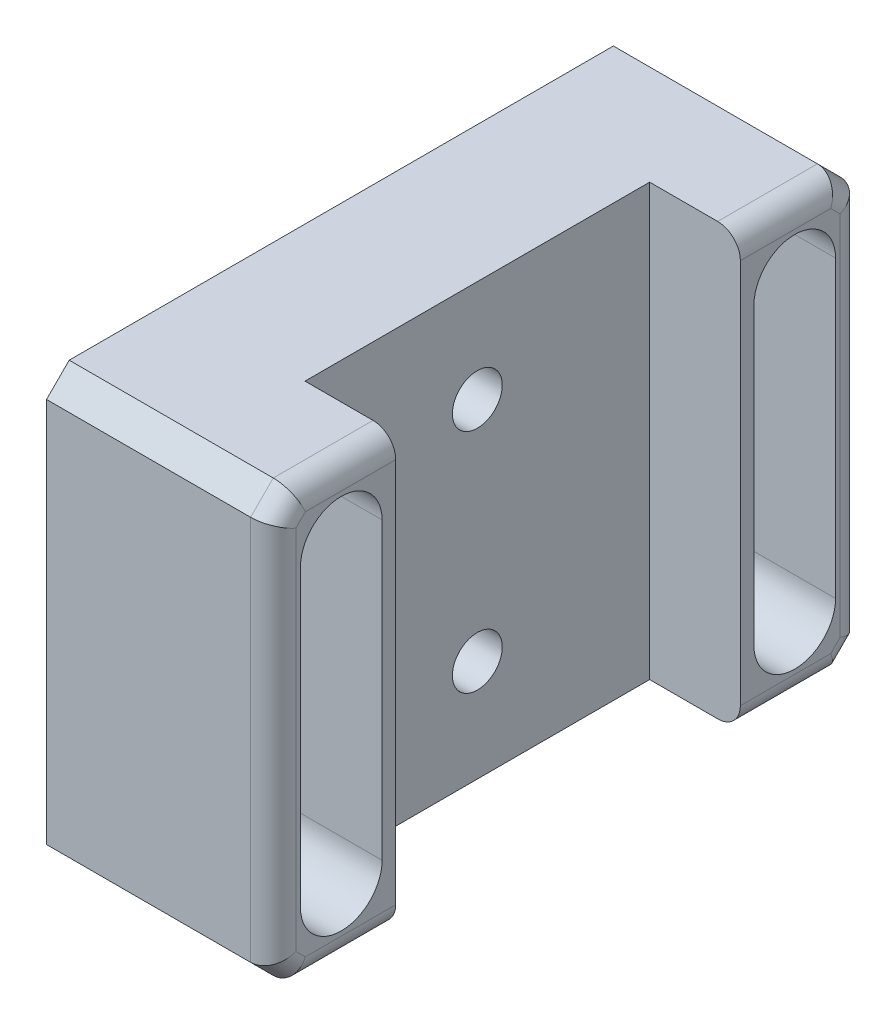
SolidWorks part; units mm, degrees
ref_plane "Спереди" through (0, 0, 0) normal (0, 0, 1) x (1, 0, 0)
ref_plane "Сверху" through (0, 0, 0) normal (0, 1, 0) x (1, 0, 0)
ref_plane "Справа" through (0, 0, 0) normal (1, 0, 0) x (0, 0, -1)
sketch "Эскиз1" plane through (0, 0, 0) normal (1, 0, 0) x (0, 0, -1)
  line L0 (-10, 6.5) -> (-10, -6.5) construction
  line L1 (-13, 9.5) -> (13, 9.5)
  line L2 (-13, 9.5) -> (-13, -9.5)
  line L3 (-13, -9.5) -> (13, -9.5)
  line L4 (13, 9.5) -> (13, -9.5)
  line L5 (-13, 9.5) -> (13, -9.5) construction
  line L6 (-13, -9.5) -> (13, 9.5) construction
  line L7 (-8.9, 6.5) -> (-8.9, -6.5)
  line L8 (-11.1, 6.5) -> (-11.1, -6.5)
  line L9 (0, 9.5) -> (0, -9.5) construction
  line L10 (10, 6.5) -> (10, -6.5) construction
  line L11 (8.9, 6.5) -> (8.9, -6.5)
  line L12 (11.1, 6.5) -> (11.1, -6.5)
  arc A0 (-8.9, 6.5) -> (-11.1, 6.5) centre (-10, 6.5) ccw
  arc A1 (-11.1, -6.5) -> (-8.9, -6.5) centre (-10, -6.5) ccw
  arc A2 (8.9, 6.5) -> (11.1, 6.5) centre (10, 6.5) cw
  arc A3 (11.1, -6.5) -> (8.9, -6.5) centre (10, -6.5) cw
  point P0 (0, 0)
  point P8 (-10, 0)
  point P17 (10, 0)
  dimension "D1" = 26
  dimension "D2" = 2.2
  dimension "D3" = 20
  dimension "D5" = 3
  dimension "D4" = 19
extrude "Бобышка-Вытянуть1" add sketch "Эскиз1" along normal blind 10
sketch "Эскиз2" plane through (10, 0, 0) normal (1, 0, 0) x (0, 0, -1)
  line L0 (-13, -9.5) -> (13, -9.5) construction
  line L1 (7.6, 9.5) -> (-7.6, 9.5)
  line L2 (7.6, 9.5) -> (7.6, -9.5)
  line L3 (7.6, -9.5) -> (-7.6, -9.5)
  line L4 (-7.6, 9.5) -> (-7.6, -9.5)
  line L5 (7.6, 9.5) -> (-7.6, -9.5) construction
  line L6 (7.6, -9.5) -> (-7.6, 9.5) construction
  point P0 (0, 0)
  dimension "D1" = 15.2
extrude "Вырез-Вытянуть1" cut sketch "Эскиз2" against normal blind 4
sketch "Эскиз3" plane through (10, 0, 0) normal (1, 0, 0) x (0, 0, -1)
  line L0 (-10, -6.5) -> (-10, 6.5) construction
  line L1 (-11.8, -6.5) -> (-11.8, 6.5)
  line L2 (-8.2, -6.5) -> (-8.2, 6.5)
  line L3 (0, 9.5) -> (0, -9.5) construction
  line L4 (7.6, 9.5) -> (-7.6, 9.5) construction
  line L5 (-7.6, -9.5) -> (7.6, -9.5) construction
  line L6 (10, -6.5) -> (10, 6.5) construction
  line L7 (11.8, -6.5) -> (11.8, 6.5)
  line L8 (8.2, -6.5) -> (8.2, 6.5)
  arc A0 (-11.8, -6.5) -> (-8.2, -6.5) centre (-10, -6.5) ccw
  arc A1 (-8.2, 6.5) -> (-11.8, 6.5) centre (-10, 6.5) ccw
  arc A2 (-11.1, -6.5) -> (-8.9, -6.5) centre (-10, -6.5) ccw construction
  arc A3 (-8.9, 6.5) -> (-11.1, 6.5) centre (-10, 6.5) ccw construction
  arc A4 (11.8, -6.5) -> (8.2, -6.5) centre (10, -6.5) cw
  arc A5 (8.2, 6.5) -> (11.8, 6.5) centre (10, 6.5) cw
  point P2 (-10, 0)
  point P23 (10, 0)
  dimension "D1" = 3.6
extrude "Вырез-Вытянуть2" cut sketch "Эскиз3" against normal blind 4
chamfer "Фаска1" distance 1 angle 45 4 edges at (5, 9.5, -13) (5, -9.5, -13) (5, -9.5, 13) (5, 9.5, 13)
fillet "Скругление1" radius 1 10 edges at (10, 9, 12.5) (10, -9, 12.5) (10, -9, -12.5) (10, -9.5, -9.8) (10, 0, -13) (10, 9, -12.5) (10, 9.5, -9.8) (10, -9.5, 9.8) (10, 9.5, 9.8) (10, 0, 13)
sketch "Эскиз4" plane through (6, 0, 0) normal (1, 0, 0) x (0, 0, -1)
  line L0 (0, 9.5) -> (0, -9.5) construction
  line L1 (7.6, 9.5) -> (-7.6, 9.5) construction
  line L2 (-7.6, -9.5) -> (7.6, -9.5) construction
  line L3 (-7.6, 0) -> (7.6, 0) construction
  line L4 (-7.6, 9.5) -> (-7.6, -9.5) construction
  line L5 (7.6, -9.5) -> (7.6, 9.5) construction
  circle A0 centre (0, 5) radius 1.1
  circle A1 centre (0, -5) radius 1.1
  dimension "D1" = 2.2
  dimension "D2" = 10
extrude "Вырез-Вытянуть3" cut sketch "Эскиз4" against normal through all
sketch "Эскиз5" plane through (0, 0, 0) normal (-1, 0, 0) x (0, 0, 1)
  line L1 (1.1258, 3.05) -> (2.2517, 5)
  line L2 (2.2517, 5) -> (1.1258, 6.95)
  line L3 (1.1258, 6.95) -> (-1.1258, 6.95)
  line L4 (-1.1258, 6.95) -> (-2.2517, 5)
  line L5 (-2.2517, 5) -> (-1.1258, 3.05)
  line L6 (-1.1258, 3.05) -> (1.1258, 3.05)
  line L7 (1.1258, -6.95) -> (2.2517, -5)
  line L8 (2.2517, -5) -> (1.1258, -3.05)
  line L9 (1.1258, -3.05) -> (-1.1258, -3.05)
  line L10 (-1.1258, -3.05) -> (-2.2517, -5)
  line L11 (-2.2517, -5) -> (-1.1258, -6.95)
  line L12 (-1.1258, -6.95) -> (1.1258, -6.95)
  circle A0 centre (0, 5) radius 1.95 construction
  circle A1 centre (0, -5) radius 1.95 construction
  dimension "D1" = 3.9
  dimension "D2" = 3.9
extrude "Вырез-Вытянуть4" cut sketch "Эскиз5" against normal blind 2.2
equation "\"motor_diameter\"= 30"
equation "\"mm_diameter\"= IIF ( \"motor_diameter\" < 34 , 41 , \"motor_diameter\" + 8 )"
equation "\"upper_shafts_diameter\"= 5"
equation "\"upper_shats_length\"= 180"
equation "\"upper_bearing_d1\"= 10"
equation "\"upper_bearing_d2\"= 5"
equation "\"upper_bearing_h\"= 15"
equation "\"lower_shafts_diameter\"= 5"
equation "\"lower_shafts_length\"= 180"
equation "\"lower_bearing_d1\"= 10"
equation "\"lower_bearing_d2\"= 5"
equation "\"lower_bearing_h\"= 15"
equation "\"print_offset\"= 0.2"
equation "\"bh_screws_d\"= 2"
equation "\"bh_screws_h\"= 20"
equation "\"bh_screws_hh_d\"= 3.4"
equation "\"bh_screws_hh_h\"= 2"
equation "\"bh_nut_d\"= 3.8"
equation "\"bh_nut_h\"= 2"
equation "\"motor_screws_d\"= 3"
equation "\"motor_screws_h\"= 16"
equation "\"motor_screws_hh_d\"= 5.5"
equation "\"motor_screws_hh_h\"= 3"
equation "\"plate_hole_distance\"= 25.4"
equation "\"plate_screws_d\"= 6.5"
equation "\"shafts_diameter\"= IIF ( \"mm_diameter\" < 42 , 42 + 8 , \"mm_diameter\" + 8 )"
equation "\"central_hole_diameter\"= 8"
equation "\"bh_thikness\"= 4"
equation "\"ends_screws_d\"= 4"
equation "\"ends_screws_h\"= 16"
equation "\"ends_screws_hh_d\"= 6.7"
equation "\"ends_screws_hh_h\"= 4.1"
equation "\"ends_nut_d\"= 6.8"
equation "\"ends_nut_h\"= 3"
equation "\"system_radius\" = ( \"shafts_diameter\" + 12 + \"bh_thikness\" / 2 ) / 2"
equation "\"encoder_distance\"= \"system_radius\" + 4"
equation "\"tape_position\"= \"encoder_distance\" - 2 + 3.9 + 1.7 / 2"
equation "\"D2@Эскиз1\"=\"bh_screws_d\"+\"print_offset\""
equation "\"D1@Бобышка-Вытянуть1\"=6"
equation "\"D4@Эскиз1\"=\"upper_bearing_h\" + 6 + 3 - 8 + 3"
equation "\"D1@Эскиз2\"=\"print_offset\"+15"
equation "\"D1@Эскиз3\"=\"bh_screws_hh_d\"+\"print_offset\""
equation "\"D1@Вырез-Вытянуть2\"=\"bh_screws_hh_h\"+2"
equation "\"D1@Эскиз4\"=\"bh_screws_d\"+\"print_offset\""
equation "\"D1@Эскиз5\"=\"bh_nut_d\"+\"print_offset\"/2"
equation "\"D2@Эскиз5\"=\"D1@Эскиз5\""
equation "\"D1@Вырез-Вытянуть4\"=\"bh_nut_h\"+\"print_offset\""
